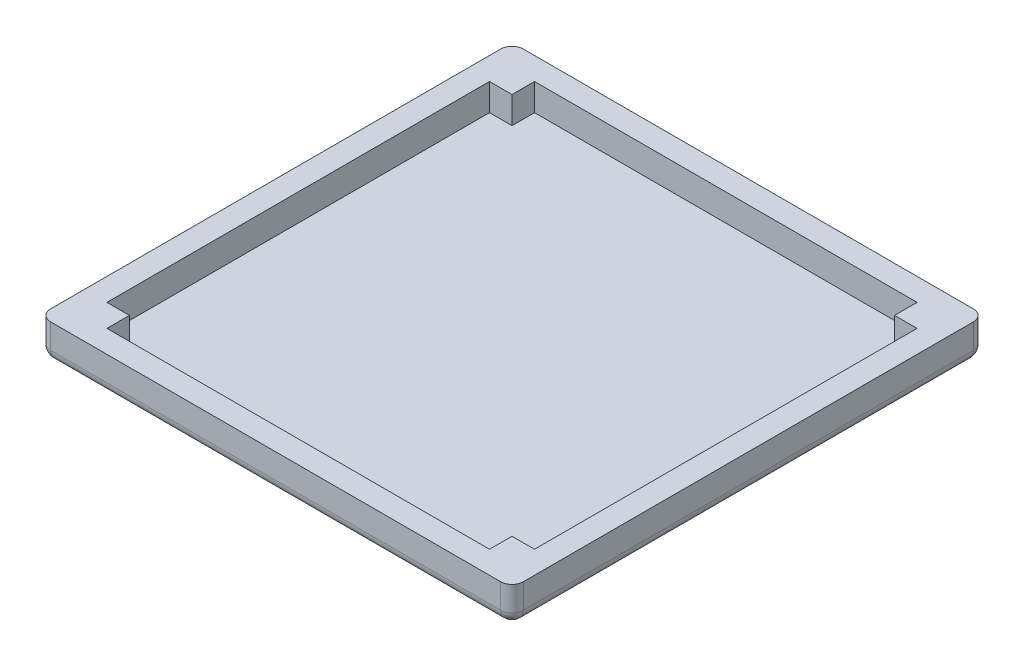
SolidWorks part; units mm, degrees
ref_plane "Front Plane" through (0, 0, 0) normal (0, 0, 1) x (1, 0, 0)
ref_plane "Top Plane" through (0, 0, 0) normal (0, 1, 0) x (1, 0, 0)
ref_plane "Right Plane" through (0, 0, 0) normal (1, 0, 0) x (0, 0, -1)
sketch "Sketch1" plane through (0, 0, 0) normal (0, 1, 0) x (1, 0, 0)
  line L1 (-105, -105) -> (105, -105)
  line L2 (-105, -105) -> (-105, 105)
  line L3 (-105, 105) -> (105, 105)
  line L4 (105, -105) -> (105, 105)
  line L5 (-105, -105) -> (105, 105) construction
  line L6 (-105, 105) -> (105, -105) construction
  point P0 (0, 0)
  dimension "D1" = 210
  dimension "D2" = 210
extrude "Base" add sketch "Sketch1" along normal blind 16
sketch "Sketch3" plane through (0, 16, 0) normal (0, 1, 0) x (1, 0, 0)
  line L0 (0, 95) -> (0, 105) construction
  line L1 (-85, 95) -> (85, 95)
  line L2 (-95, 85) -> (-95, -85)
  line L3 (-85, -95) -> (85, -95)
  line L4 (95, 85) -> (95, -85)
  line L5 (-95, 95) -> (95, -95) construction
  line L6 (-95, -95) -> (95, 95) construction
  line L7 (105, 105) -> (-105, 105) construction
  line L8 (95, 0) -> (105, 0) construction
  line L9 (105, -105) -> (105, 105) construction
  line L10 (0, -95) -> (0, -105) construction
  line L11 (-105, -105) -> (105, -105) construction
  line L12 (-95, 0) -> (-105, 0) construction
  line L13 (-105, 105) -> (-105, -105) construction
  line L14 (95, -95) -> (95, -85) construction
  line L17 (-95, 85) -> (-85, 85)
  line L18 (-85, 95) -> (-85, 85)
  line L21 (95, -85) -> (85, -85)
  line L22 (85, -95) -> (85, -85)
  line L25 (95, 85) -> (85, 85)
  line L26 (85, 95) -> (85, 85)
  line L29 (-95, -85) -> (-85, -85)
  line L30 (-85, -95) -> (-85, -85)
  line L31 (95, -95) -> (85, -95) construction
  line L32 (-95, -95) -> (-95, -85) construction
  line L33 (-95, 95) -> (-85, 95) construction
  line L34 (-95, 85) -> (-95, 95) construction
  line L35 (95, 95) -> (85, 95) construction
  line L36 (95, 85) -> (95, 95) construction
  line L37 (-95, -95) -> (-85, -95) construction
  point P0 (0, 0)
  dimension "D1" = 10
  dimension "D2" = 10
extrude "Cut-Extrude1" cut sketch "Sketch3" against normal blind 12
fillet "Fillet1" radius 5 4 edges at (0, 0, -105) (-105, 0, 0) (0, 0, 105) (105, 0, 0)
fillet "Fillet2" radius 5 8 edges at (-103.5355, 1.4645, 103.5355) (-105, 10.5, 105) (103.5355, 1.4645, -103.5355) (103.5355, 1.4645, 103.5355) (-103.5355, 1.4645, -103.5355) (105, 10.5, -105) (105, 10.5, 105) (-105, 10.5, -105)
equation "\"Width\"=210"
equation "\"D1@Sketch1\"=\"Width\""
equation "\"Depth\"=210"
equation "\"D2@Sketch1\"=\"Depth\""
equation "\"height\"=16"
equation "\"D1@Base\"=\"height\""
equation "\"r1\"=5"
equation "\"D1@Fillet2\"=\"r1\""
equation "\"D1@Fillet1\"=\"r1\""
